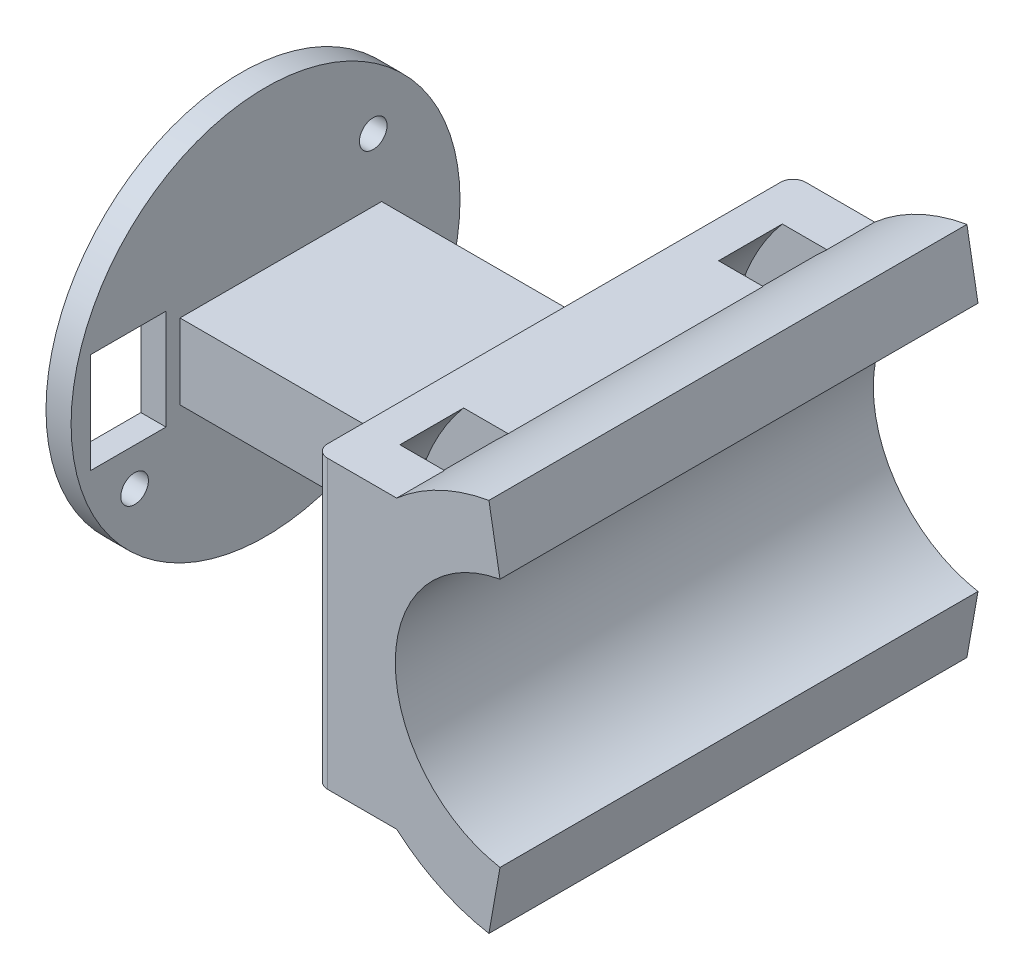
SolidWorks part; units mm, degrees
ref_plane "Top Plane" through (0, 0, 0) normal (0, 0, 1) x (1, 0, 0)
ref_plane "Right Plane" through (0, 0, 0) normal (0, 1, 0) x (1, 0, 0)
ref_plane "Front Plane" through (0, 0, 0) normal (1, 0, 0) x (0, 0, -1)
ref_axis "x-axis" through (-88.99, 0, 0) along (1, 0, 0)
ref_axis "y-axis" through (0, -55, 0) along (0, 1, 0)
ref_axis "z-axis" through (0, 0, 55) along (0, 0, -1)
sketch "Sketch1" plane through (0, 0, 0) normal (0, 0, 1) x (1, 0, 0)
  line L0 (8.3462, -9.9466) -> (7.464, -14.9494)
  line L2 (8.3462, -9.9466) -> (10.1, 0) construction
  line L4 (10.1, 0) -> (8.3462, 9.9466) construction
  line L5 (8.3462, 9.9466) -> (7.464, 14.9494)
  line L6 (20.955, 0) -> (-20.955, 0) construction
  line L7 (8.3462, -9.9466) -> (8.3462, 9.9466) construction
  line L8 (0, 0) -> (-6.3894, 0) construction
  line L11 (0.1106, 11.43) -> (-6.3894, 11.43)
  line L12 (-6.3894, -11.43) -> (-6.3894, 11.43)
  line L13 (0.1106, -11.43) -> (-6.3894, -11.43) construction
  line L22 (0.1106, -11.43) -> (-6.3894, -11.43)
  arc A0 (8.3462, -9.9466) -> (8.3462, 9.9466) centre (10.1, 0) cw
  arc A1 (7.464, -14.9494) -> (0.1106, -11.43) centre (10.1, 0) cw
  arc A2 (0.1106, 11.43) -> (7.464, 14.9494) centre (10.1, 0) cw
  dimension "D1" = 160
  dimension "D2" = 5.08
  dimension "D3" = 10.1
  dimension "D4" = 6.5
  dimension "D5" = 22.86
extrude "Boss-Extrude1" add sketch "Sketch1" along normal mid plane 38.1
ref_axis "Axis2" through (10.1, 0, 19.05) along (0, 0, -1)
sketch "Sketch6" plane through (-6.3894, 0, 0) normal (-1, 0, 0) x (0, 0, 1)
  line L12 (-9.2494, -3) -> (6.822, -3)
  line L13 (-9.2494, -3) -> (-9.2494, 3)
  line L14 (-9.2494, 3) -> (6.822, 3)
  line L15 (6.822, -3) -> (6.822, 3)
  line L16 (-4.7767, 0) -> (-4.7767, -3) construction
  line L17 (19.05, 0) -> (-19.05, 0) construction
  line L18 (-2.6665, 0) -> (-2.6665, 3) construction
  dimension "D1" = 6
extrude "Boss-Extrude3" add sketch "Sketch6" along normal blind 23
sketch "Sketch3" plane through (0, 0, 0) normal (0, 1, 0) x (1, 0, 0)
  line L0 (0, -12.7) -> (0, 12.7) construction
  line L1 (-5.08, 12.7) -> (0, 12.7) construction
  line L2 (-7.62, 15.24) -> (-5.08, 15.24)
  line L3 (-7.62, 15.24) -> (-7.62, 10.16)
  line L4 (-7.62, 10.16) -> (-5.08, 10.16)
  line L5 (-5.08, 15.24) -> (-5.08, 10.16)
  line L6 (-7.62, 15.24) -> (-5.08, 15.24)
  line L7 (-7.62, 10.16) -> (-5.08, 10.16)
  line L8 (-6.3885, 0) -> (6.3885, 0) construction
  line L9 (-5.08, -12.7) -> (0, -12.7) construction
  line L10 (-5.08, -15.24) -> (-5.08, -10.16)
  line L11 (-7.62, -10.16) -> (-5.08, -10.16)
  line L12 (-7.62, -15.24) -> (-7.62, -10.16)
  line L13 (-7.62, -15.24) -> (-5.08, -15.24)
  point P4 (0, 0)
  dimension "D1" = 5.08
  dimension "D2" = 2.54
  dimension "D3" = 5.08
  dimension "D4" = 25.4
revolve "Cut-Revolve1" cut sketch "Sketch3" angle 360 about axis through (10.1, 0, 19.05) along (0, 0, -1) region at (-6.35, 0, -12.7) region at (-6.35, 0, 12.7)
sketch "Sketch5" plane through (-6.3894, 0, 0) normal (-1, 0, 0) x (0, -1, 0)
  line L0 (11.43, 19.05) -> (11.43, -19.05) construction
  line L1 (-11.43, 19.05) -> (11.43, 19.05)
  line L2 (-11.43, 19.05) -> (-11.43, -5.3894)
  line L3 (-11.43, -5.3894) -> (11.43, -5.3894)
  line L4 (11.43, 19.05) -> (11.43, -5.3894)
sketch "Sketch4" plane through (-29.3894, 0, 0) normal (-1, 0, 0) x (0, -1, 0)
  line L0 (0, 19.05) -> (0, -19.05) construction
  line L5 (-4, 7.9307) -> (0, 7.9307) construction
  line L6 (0, 7.0768) -> (4, 7.0768) construction
  line L7 (0, -14) -> (0, -15.5) construction
  line L8 (-0.0257, 13.9362) -> (-0.0257, 15.4362) construction
  line L9 (-4.0257, 13.9362) -> (3.9743, 13.9362)
  line L10 (-4.0257, 13.9362) -> (-4.0257, 7.9362)
  line L11 (-4.0257, 7.9362) -> (3.9743, 7.9362)
  line L12 (3.9743, 13.9362) -> (3.9743, 7.9362)
  line L13 (-4.0257, 9.9362) -> (-7.0257, 9.9362) construction
  line L14 (6.9743, 10.436) -> (3.9743, 10.436) construction
  circle A0 centre (0, 0) radius 15.5
  circle A3 centre (6.9743, 10.436) radius 1.1
  circle A5 centre (-8.0257, -8.5809) radius 1.0993
  dimension "D1" = 31
  dimension "D2" = 2
  dimension "D3" = 2.4998
  dimension "D4" = 1.5
extrude "Boss-Extrude2" add sketch "Sketch4" along normal blind 2
fillet "Fillet1" radius 1 2 edges at (-6.3894, 0, -19.05) (-6.3894, 0, 19.05)
